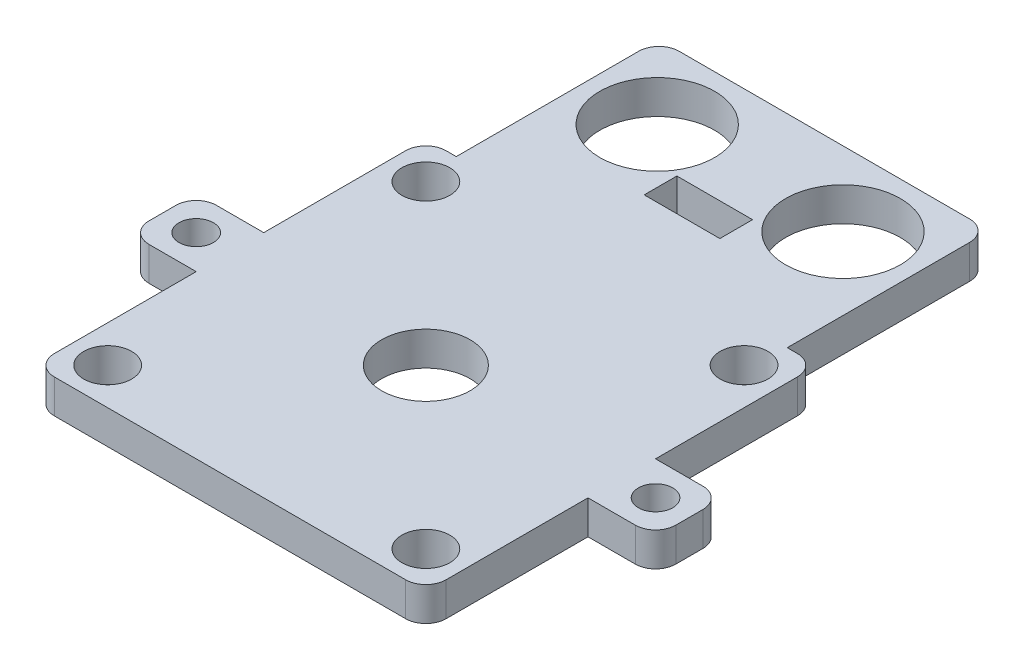
SolidWorks part; units mm, degrees
ref_plane "Front Plane" through (0, 0, 0) normal (0, 0, 1) x (1, 0, 0)
ref_plane "Top Plane" through (0, 0, 0) normal (0, 1, 0) x (1, 0, 0)
ref_plane "Right Plane" through (0, 0, 0) normal (1, 0, 0) x (0, 0, -1)
sketch "Sketch1" plane through (0, 0, 0) normal (0, 1, 0) x (1, 0, 0)
  circle A0 centre (0, 0) radius 20
  circle A1 centre (0, 0) radius 21
  dimension "D1" = 40
  dimension "D2" = 42
extrude "Boss-Extrude1" add sketch "Sketch1" along normal blind 3.5
ref_plane "Plane1" through (0, 3.5, 0) normal (0, 1, 0) x (1, 0, 0)
sketch "Sketch2" plane through (0, 3.5, 0) normal (0, 1, 0) x (1, 0, 0)
  line L0 (-23.55, 0) -> (23.55, 0) construction
  line L1 (-29, -29) -> (29, -29)
  line L2 (-29, -29) -> (-29, 29)
  line L3 (-29, 29) -> (29, 29)
  line L4 (29, -29) -> (29, 29)
  line L5 (-29, -29) -> (29, 29) construction
  line L6 (-29, 29) -> (29, -29) construction
  line L7 (-28.2, -28.2) -> (28.2, -28.2) construction
  line L8 (-28.2, -28.2) -> (-28.2, 28.2) construction
  line L9 (-28.2, 28.2) -> (28.2, 28.2) construction
  line L10 (28.2, -28.2) -> (28.2, 28.2) construction
  line L11 (-28.2, -28.2) -> (28.2, 28.2) construction
  line L12 (-28.2, 28.2) -> (28.2, -28.2) construction
  line L13 (-23.55, 28.2) -> (-23.55, 23.55) construction
  line L14 (-23.55, 23.55) -> (-28.2, 23.55) construction
  line L15 (0, 28.2) -> (0, -28.2) construction
  line L16 (0, 29) -> (0, 49) construction
  line L17 (-22.5, 49) -> (22.5, 49) construction
  line L18 (-22.5, 49) -> (-22.5, 29) construction
  line L19 (22.5, 49) -> (22.5, 29) construction
  line L20 (0, 49) -> (0, 48) construction
  line L21 (-4.9, 48) -> (4.9, 48) construction
  line L22 (-4.9, 48) -> (-4.9, 44.56) construction
  line L23 (-4.9, 44.56) -> (4.9, 44.56) construction
  line L24 (4.9, 44.56) -> (4.9, 48) construction
  line L25 (-24.5, 29) -> (-24.5, 51)
  line L26 (-24.5, 51) -> (24.5, 51)
  line L27 (24.5, 51) -> (24.5, 29)
  line L28 (-13.76, 39) -> (13.76, 39) construction
  line L29 (-5.6, 48.7) -> (5.6, 48.7)
  line L31 (5.6, 43.86) -> (-5.6, 43.86)
  line L32 (-5.6, 43.86) -> (-5.6, 48.7)
  line L33 (5.6, 43.86) -> (5.6, 48.7)
  line L34 (-24.5, 51) -> (-24.5, 59)
  line L35 (-24.5, 59) -> (24.5, 59)
  line L36 (24.5, 59) -> (24.5, 51)
  line L37 (0, 0) -> (34, 0) construction
  line L38 (29, 5) -> (39, 5)
  line L39 (29, -5) -> (39, -5)
  line L40 (39, 5) -> (39, -5)
  line L41 (-29, -5) -> (-39, -5)
  line L42 (-39, 5) -> (-39, -5)
  line L43 (-29, 5) -> (-39, 5)
  circle A0 centre (-23.55, 23.55) radius 2.55 construction
  circle A1 centre (23.55, 23.55) radius 2.55 construction
  circle A2 centre (23.55, -23.55) radius 2.55 construction
  circle A3 centre (-23.55, -23.55) radius 2.55 construction
  circle A4 centre (0, 0) radius 5.5563 construction
  circle A5 centre (13.76, 39) radius 7.5 construction
  circle A6 centre (-13.76, 39) radius 7.5 construction
  circle A7 centre (-13.76, 39) radius 8.5
  circle A8 centre (13.76, 39) radius 8.5
  circle A9 centre (0, 0) radius 6.55
  circle A10 centre (-23.55, 23.55) radius 3.55
  circle A11 centre (23.55, 23.55) radius 3.55
  circle A12 centre (23.55, -23.55) radius 3.55
  circle A13 centre (-23.55, -23.55) radius 3.55
  circle A14 centre (34, 0) radius 2.55
  circle A15 centre (-34, 0) radius 2.55
  point P0 (0, 0)
  point P5 (0, 0)
  point P15 (0, 0)
  point P34 (0, 49)
  point P40 (0, 48)
  point P49 (0, 39)
  point P56 (0, 43.86)
  point P59 (0, 48.7)
  point P70 (34, 0)
  dimension "D4" = 5.1
  dimension "D5" = 11.1125
  dimension "D15" = 15
  dimension "D16" = 17
  dimension "D17" = 0.7
  dimension "D20" = 13.1
  dimension "D21" = 7.1
  dimension "D22" = 8
  dimension "D24" = 5.1
  dimension "D25" = 5
  dimension "D1" = 58
  dimension "D2" = 56.4
  dimension "D3" = 47.1
  dimension "D6" = 20
  dimension "D7" = 45
  dimension "D8" = 1
  dimension "D9" = 9.8
  dimension "D10" = 3.44
  dimension "D11" = 2
  dimension "D12" = 2
  dimension "D13" = 2
  dimension "D14" = 27.52
  dimension "D18" = 0.7
  dimension "D19" = 0.7
  dimension "D23" = 34
  dimension "D26" = 5
extrude "Boss-Extrude2" add sketch "Sketch2" along normal blind 5 contours L1 L4 L3 L2 A4 A1 A0 A2 A3 | L27 L26 L25 L3 A8 A7 L33 L31 L32 L29 | L40 L38 L4 L39 A14 | L2 L43 L42 L41 A15 region at (-28.1798, 3.5, 17) region at (-34, 3.5, 4.8586) region at (29.1414, 3.5, 0) region at (0, 3.5, -40.1992)
sketch "Sketch3" plane through (0, 3.5, 0) normal (0, 1, 0) x (1, 0, 0)
  line L0 (-5.6, 48.7) -> (5.6, 48.7)
  line L1 (5.6, 48.7) -> (5.6, 43.86)
  line L2 (5.6, 43.86) -> (-5.6, 43.86)
  line L3 (-5.6, 43.86) -> (-5.6, 48.7)
  line L4 (-13.76, 47.5) -> (-13.76, 30.5) construction
  line L5 (13.76, 47.5) -> (13.76, 30.5) construction
  line L6 (-24.5, 29) -> (24.5, 29)
  line L7 (24.5, 29) -> (24.5, 51)
  line L8 (24.5, 51) -> (-24.5, 51)
  line L9 (-24.5, 51) -> (-24.5, 29)
  line L10 (-24.5, 51) -> (-24.5, 59)
  line L11 (-24.5, 59) -> (24.5, 59)
  line L12 (24.5, 59) -> (24.5, 51)
  circle A0 centre (-13.76, 39) radius 8.5 construction
  circle A1 centre (-13.76, 39) radius 8.5
  circle A2 centre (13.76, 39) radius 8.5 construction
  circle A3 centre (13.76, 39) radius 8.5
  dimension "D1" = 8
sketch "Sketch4" plane through (0, 3.5, 0) normal (0, 1, 0) x (1, 0, 0)
  line L4 (-5.6791, 42.84) -> (-5.6791, 38)
  line L5 (5.5209, 38) -> (5.5209, 42.84)
  line L10 (-24.5, 29) -> (-24.5, 37)
  line L11 (-24.5, 51) -> (-24.5, 29) construction
  line L12 (24.5, 29) -> (24.5, 37)
  line L13 (24.5, 29) -> (24.5, 51) construction
  line L14 (-24.5, 37) -> (-24.5, 59)
  line L15 (24.5, 37) -> (24.5, 59)
  line L16 (-24.5, 59) -> (24.5, 59)
  line L17 (-24.5, 37) -> (24.5, 37)
  line L18 (0, 59) -> (0, 37) construction
  line L23 (-5.6791, 38) -> (5.5209, 38)
  line L24 (5.5209, 42.84) -> (-5.6791, 42.84)
  line L25 (-5.6791, 58) -> (5.5209, 58) construction
  line L26 (5.5209, 58) -> (5.5209, 53.16) construction
  line L27 (5.5209, 53.16) -> (-5.6791, 53.16) construction
  line L28 (-5.6791, 53.16) -> (-5.6791, 58) construction
  line L29 (-13.75, 56.5) -> (-13.75, 39.5) construction
  line L30 (-13.75, 48) -> (13.75, 48) construction
  circle A4 centre (-13.75, 48) radius 8.5
  circle A5 centre (13.75, 48) radius 8.5
  point P53 (0, 48)
  dimension "D2" = 17
  dimension "D1" = 8
  dimension "D3" = 22
  dimension "D4" = 1
  dimension "D5" = 5.5209
  dimension "D6" = 11.2
  dimension "D7" = 4.84
  dimension "D8" = 27.5
extrude "Ignore" add sketch "Sketch3" along normal blind 5 contours L3 L2 L1 L0 | L12 L11 L10 L8 | A3 | A1 region at (0, 3.5, -46.28) region at (0, 3.5, -55) region at (-13.76, 3.5, -39) region at (13.76, 3.5, -39)
extrude "Cut-Extrude2" cut sketch "Sketch4" along normal through all contours A4 | A5 | L28 L27 L26 L25 | L5 L24 L4 L23 region at (-0.0791, 3.5, -40.42) region at (-13.75, 3.5, -48) region at (13.75, 3.5, -48)
fillet "Fillet1" radius 3 10 edges at (29, 6, -29) (39, 6, 5) (39, 6, -5) (29, 6, 29) (-29, 6, 29) (-39, 6, 5) (-39, 6, -5) (-29, 6, -29) (24.5, 6, -59) (-24.5, 6, -59)
sketch "Sketch5" plane through (0, 0, 0) normal (0, 0, 1) x (1, 0, 0)
  line L0 (-21, 3.5) -> (21, 3.5)
  line L1 (21, 3.5) -> (21, 0)
  line L2 (21, 0) -> (-21, 0)
  line L3 (-21, 0) -> (-21, 3.5)
extrude "Cut-Extrude3" cut sketch "Sketch5" against normal mid plane 50
